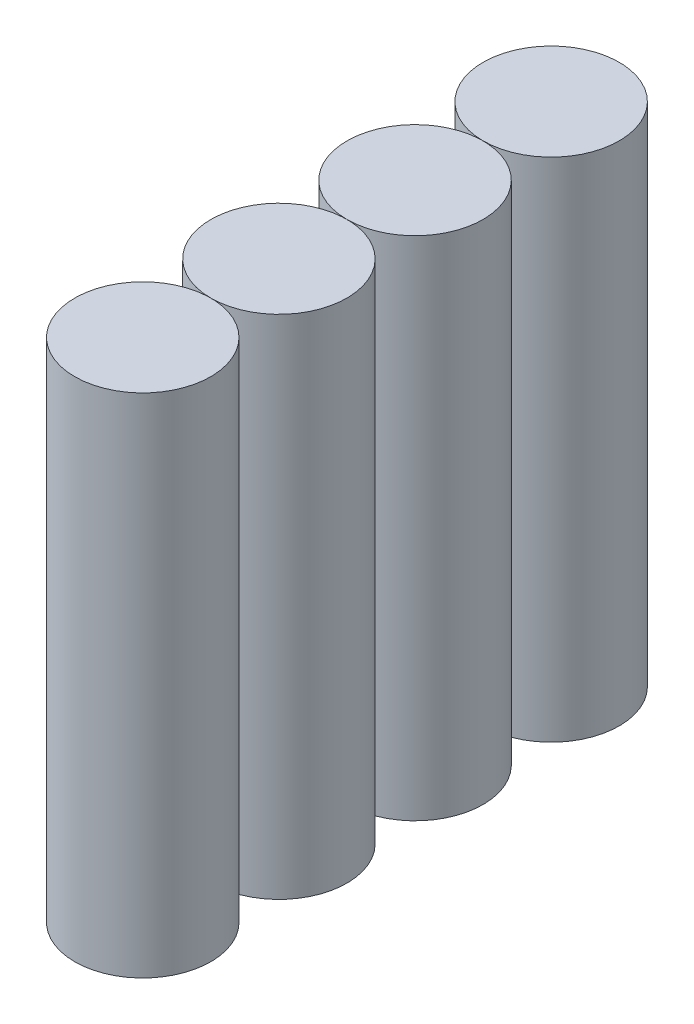
SolidWorks part; units mm, degrees
ref_plane "Front Plane" through (0, 0, 0) normal (0, 0, 1) x (1, 0, 0)
ref_plane "Top Plane" through (0, 0, 0) normal (0, 1, 0) x (1, 0, 0)
ref_plane "Right Plane" through (0, 0, 0) normal (1, 0, 0) x (0, 0, -1)
sketch "Sketch1" plane through (0, 0, 0) normal (0, 1, 0) x (1, 0, 0)
  line L0 (-25.3682, 23.0203) -> (-25.3682, -52.0342) construction
  circle A0 centre (-16.3682, -10.5653) radius 9
  circle A1 centre (-16.3682, -28.5653) radius 9
  circle A2 centre (-16.3682, -46.5653) radius 9
  circle A4 centre (-16.3682, -64.5653) radius 9
  dimension "D1" = 18
extrude "Boss-Extrude1" add sketch "Sketch1" against normal blind 67 contours A4 | A2 | A1 | A0
